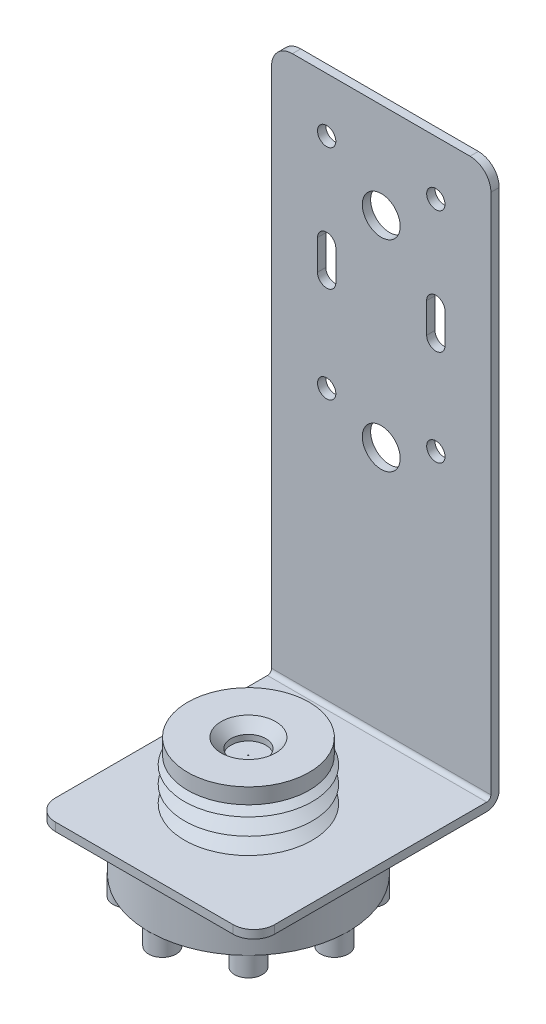
SolidWorks part; units mm, degrees
ref_plane "Front" through (0, 0, 0) normal (0, 0, 1) x (1, 0, 0)
ref_plane "Top" through (0, 0, 0) normal (0, 1, 0) x (1, 0, 0)
ref_plane "Right" through (0, 0, 0) normal (1, 0, 0) x (0, 0, -1)
sketch "Sketch1" plane through (0, 0, 0) normal (1, 0, 0) x (0, 0, -1)
  line L0 (0, 101.6) -> (0, 0)
  line L1 (0, 0) -> (-44.9072, 0)
  dimension "D1" = 101.6
  dimension "D2" = 44.9072
extrude "Extrude-Thin1" add sketch "Sketch1" along normal mid plane 40.132 thin thin type one direction wall 1.524
sketch "Sketch5" plane through (0, 0, 0) normal (0, 0, 1) x (1, 0, 0)
  line L0 (-11.6649, 74.7522) -> (-11.6649, 69.2522)
  line L1 (0, 0) -> (0, 101.6) construction
  line L2 (20.066, 0) -> (-20.066, 0) construction
  line L3 (-8.3121, 69.2522) -> (-8.3121, 74.7522)
  line L5 (11.6649, 74.7522) -> (11.6649, 69.2522)
  line L6 (8.3121, 69.2522) -> (8.3121, 74.7522)
  line L7 (-8.3121, 72.0022) -> (-11.6649, 72.0022) construction
  line L8 (20.066, 101.6) -> (-20.066, 101.6) construction
  line L9 (-9.9885, 93.3526) -> (-9.9885, 101.6) construction
  line L10 (-9.9885, 76.4286) -> (9.9885, 76.4286) construction
  line L11 (-9.9885, 53.3654) -> (9.9885, 53.3654) construction
  line L12 (0, 50.7746) -> (20.066, 50.7746) construction
  line L13 (20.066, 101.6) -> (20.066, 2.286) construction
  line L14 (0, 87.5538) -> (-20.066, 87.5538) construction
  line L15 (-20.066, 101.6) -> (-20.066, 2.286) construction
  circle A0 centre (-9.9885, 91.6762) radius 1.6764
  circle A1 centre (-9.9885, 51.689) radius 1.6764
  arc A2 (-8.3121, 74.7522) -> (-11.6649, 74.7522) centre (-9.9885, 74.7522) ccw
  arc A3 (-11.6649, 69.2522) -> (-8.3121, 69.2522) centre (-9.9885, 69.2522) ccw
  circle A4 centre (9.9885, 51.689) radius 1.6764
  circle A5 centre (9.9885, 91.6762) radius 1.6764
  arc A6 (11.6649, 74.7522) -> (8.3121, 74.7522) centre (9.9885, 74.7522) ccw
  arc A7 (8.3121, 69.2522) -> (11.6649, 69.2522) centre (9.9885, 69.2522) ccw
  circle A8 centre (0, 84.0867) radius 3.4671
  circle A9 centre (0, 47.3075) radius 3.4671
  dimension "D1" = 19.9771
  dimension "D3" = 3.3528
  dimension "D8" = 6.9342
  dimension "D6" = 25.1714
  dimension "D5" = 5.5
  dimension "D7" = 50.8254
  dimension "D2" = 48.2346
  dimension "D4" = 8.2474
  dimension "D9" = 14.0462
extrude "Extrude3" cut sketch "Sketch5" along normal through all
sketch "Sketch6" plane through (0, 1.524, 0) normal (0, 1, 0) x (1, 0, 0)
  line L0 (0, -16.6878) -> (20.066, -16.6878) construction
  line L1 (20.066, -2.286) -> (20.066, -44.9072) construction
  line L2 (20.066, 0) -> (-20.066, 0) construction
  circle A0 centre (0, -25.8318) radius 9.144
  dimension "D1" = 18.288
  dimension "D2" = 16.6878
extrude "Extrude4" cut sketch "Sketch6" against normal through all
ref_axis "Axis1" through (0, 0, 25.8318) along (0, 1, 0)
sketch "Sketch8" plane through (0, 0, 0) normal (1, 0, 0) x (0, 0, -1)
  line L0 (-25.9207, 10.6934) -> (-25.9207, -8.128)
  line L1 (-25.9207, -8.128) -> (-44.0817, -8.128)
  line L2 (-44.0817, -8.128) -> (-44.0817, 0)
  line L3 (-2.286, 0) -> (-44.9072, 0) construction
  line L4 (-44.0817, 0) -> (-34.7218, 0)
  line L5 (-34.7218, 0) -> (-34.7218, 1.524)
  line L6 (-2.286, 1.524) -> (-44.9072, 1.524) construction
  line L7 (-34.7218, 1.524) -> (-37.5158, 3.0522)
  line L8 (-37.5158, 3.0522) -> (-34.7218, 4.5805)
  line L9 (-34.7218, 4.5805) -> (-37.5158, 6.1087)
  line L10 (-37.5158, 6.1087) -> (-34.7218, 7.6369)
  line L11 (-34.7218, 7.6369) -> (-37.5158, 9.1652)
  line L12 (-37.5158, 9.1652) -> (-34.7218, 10.6934)
  line L13 (-34.7218, 10.6934) -> (-25.9207, 10.6934)
  line L14 (-25.8318, 0) -> (-25.8318, 1.524) construction
  line L15 (-25.8318, -2.7652) -> (-25.8318, 14.3811) construction
  dimension "D1" = 18.161
  dimension "D2" = 23.368
  dimension "D3" = 36.4998
  dimension "D4" = 8.128
  dimension "D5" = 9.1694
  dimension "D6" = 17.78
revolve "Revolve1" add sketch "Sketch8" angle 360 about L15
sketch "Sketch9" plane through (0, -8.128, 0) normal (0, -1, 0) x (1, 0, 0)
  line L0 (0, 25.8318) -> (0, 41.5798) construction
  circle A0 centre (0, 35.2298) radius 2.54 construction
  circle A1 centre (0, 41.5798) radius 2.54
  dimension "D1" = 5.08
  dimension "D2" = 6.35
  dimension "D3" = 15.748
extrude "Extrude5" add sketch "Sketch9" along normal blind 3.556
pattern_circular "CirPattern1" count 8 over 360 about axis through (0, 0, 25.8318) along (0, 1, 0) of "Extrude5"
sketch "Sketch10" plane through (0, 0, 0) normal (1, 0, 0) x (0, 0, -1)
  line L0 (-36.957, 13.5382) -> (-30.8156, 13.5382)
  line L1 (-29.0195, 11.7421) -> (-29.0195, -9.652)
  line L2 (-29.0195, -9.652) -> (-30.7848, -9.652)
  line L3 (-30.7848, -9.652) -> (-30.7848, 10.6934)
  line L4 (-30.7848, 10.6934) -> (-36.957, 10.6934)
  line L5 (-36.957, 10.6934) -> (-36.957, 13.5382)
  line L6 (-16.9418, 10.6934) -> (-34.7218, 10.6934) construction
  line L7 (-25.8318, 0.9506) -> (-25.8318, 24.4331) construction
  line L8 (-25.8318, 0) -> (-25.8318, 1.524) construction
  line L9 (-30.8156, 13.5382) -> (-29.0195, 11.7421)
  dimension "D1" = 23.1902
  dimension "D2" = 2.8448
  dimension "D3" = 6.3754
  dimension "D4" = 22.2504
  dimension "D5" = 9.906
  dimension "D6" = 45
  dimension "D7" = 2.54
revolve "Revolve2" add sketch "Sketch10" angle 360 about L7
fillet "Fillet1" radius 3.81 4 edges at (-20.066, 101.6, 0.762) (20.066, 101.6, 0.762) (-20.066, 0.762, 44.9072) (20.066, 0.762, 44.9072)
sketch "Sketch11" plane through (0, -8.128, 0) normal (0, -1, 0) x (1, 0, 0)
  line L0 (-15.748, 25.8318) -> (-8.128, 25.8318) construction
  circle A0 centre (-8.128, 25.8318) radius 2.54
  circle A4 centre (-15.748, 25.8318) radius 2.54 construction
  arc A5 (-18.2438, 25.36) -> (-18.2438, 26.3036) centre (-15.748, 25.8318) ccw construction
  circle A6 centre (0, 33.9598) radius 2.54
  circle A7 centre (8.128, 25.8318) radius 2.54
  circle A8 centre (0, 17.7038) radius 2.54
  point P17 (0, 25.8318)
  dimension "D1" = 7.62
  dimension "D2" = 4
extrude "Boss-Extrude1" add sketch "Sketch11" along normal blind 3.556
